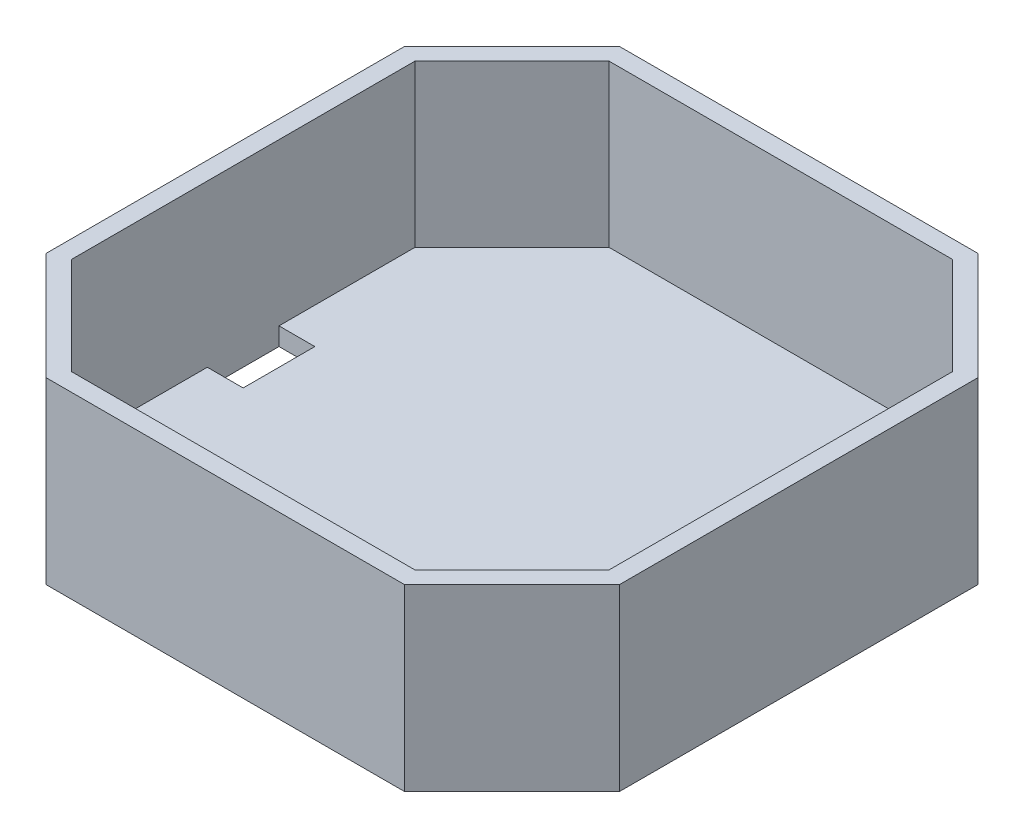
SolidWorks part; units mm, degrees
ref_plane "Front Plane" through (0, 0, 0) normal (0, 0, 1) x (1, 0, 0)
ref_plane "Top Plane" through (0, 0, 0) normal (0, 1, 0) x (1, 0, 0)
ref_plane "Right Plane" through (0, 0, 0) normal (1, 0, 0) x (0, 0, -1)
sketch "Sketch1" plane through (0, 0, 0) normal (0, 1, 0) x (1, 0, 0)
  line L0 (-80, 50) -> (-50, 80)
  line L1 (-80, 80) -> (80, 80)
  line L2 (-80, 80) -> (-80, -80)
  line L3 (-80, -80) -> (80, -80)
  line L4 (80, 80) -> (80, -80)
  line L5 (-80, 80) -> (80, -80) construction
  line L6 (-80, -80) -> (80, 80) construction
  line L7 (50, 80) -> (80, 50)
  line L8 (80, -50) -> (50, -80)
  line L9 (-50, -80) -> (-80, -50)
  point P0 (0, 0)
  point P11 (0, 0)
  point P14 (0, 0)
  point P17 (0, 0)
  point P20 (0, 0)
  dimension "D1" = 160
  dimension "D2" = 45
  dimension "D3" = 30
  dimension "D4" = 4
extrude "Boss-Extrude1" add sketch "Sketch1" along normal blind 50 contours L9 L3 L8 L4 L7 L1 L0 L2 region at (0, 0, 0)
shell "Shell1" thickness 5 removed face at (0, 50, 0)
sketch "Sketch5" plane through (0, 5, 0) normal (0, 1, 0) x (1, 0, 0)
  line L0 (-75, 47.9289) -> (-75, -47.9289) construction
  line L1 (-75, 10) -> (-65, 10)
  line L2 (-75, 10) -> (-75, -10)
  line L3 (-75, -10) -> (-65, -10)
  line L4 (-65, 10) -> (-65, -10)
  point P4 (-75, 0)
  point P7 (-75, 0)
  dimension "D1" = 20
  dimension "D2" = 10
extrude "Cut-Extrude1" cut sketch "Sketch5" against normal up to surface (5 mm away) up to face at (0, 0, 0)
sketch "Sketch6" plane through (0, 0, 80) normal (0, 0, 1) x (1, 0, 0)
  circle A0 centre (-29, 10) radius 1.6 construction
  circle A1 centre (-41, 10) radius 1.6 construction
  circle A2 centre (-29, 27) radius 1.6 construction
  circle A3 centre (-41, 27) radius 1.6 construction
  circle A4 centre (-29, 44) radius 1.6 construction
  circle A5 centre (-41, 44) radius 1.6 construction
  circle A6 centre (-29, 10) radius 1.6
  circle A7 centre (-41, 10) radius 1.6
  circle A8 centre (-29, 27) radius 1.6
  circle A9 centre (-41, 27) radius 1.6
  circle A10 centre (-29, 44) radius 1.6
  circle A11 centre (-41, 44) radius 1.6
extrude "Cut-Extrude2" [suppressed] cut sketch "Sketch6" against normal up to surface (5 mm away)
ref_axis "Axis1" through (0, 52.5, 0) along (0, -1, 0)
pattern_circular "CirPattern1" [suppressed] count 4 every 90 about axis through (0, 52.5, 0) along (0, -1, 0) of bodies 104
